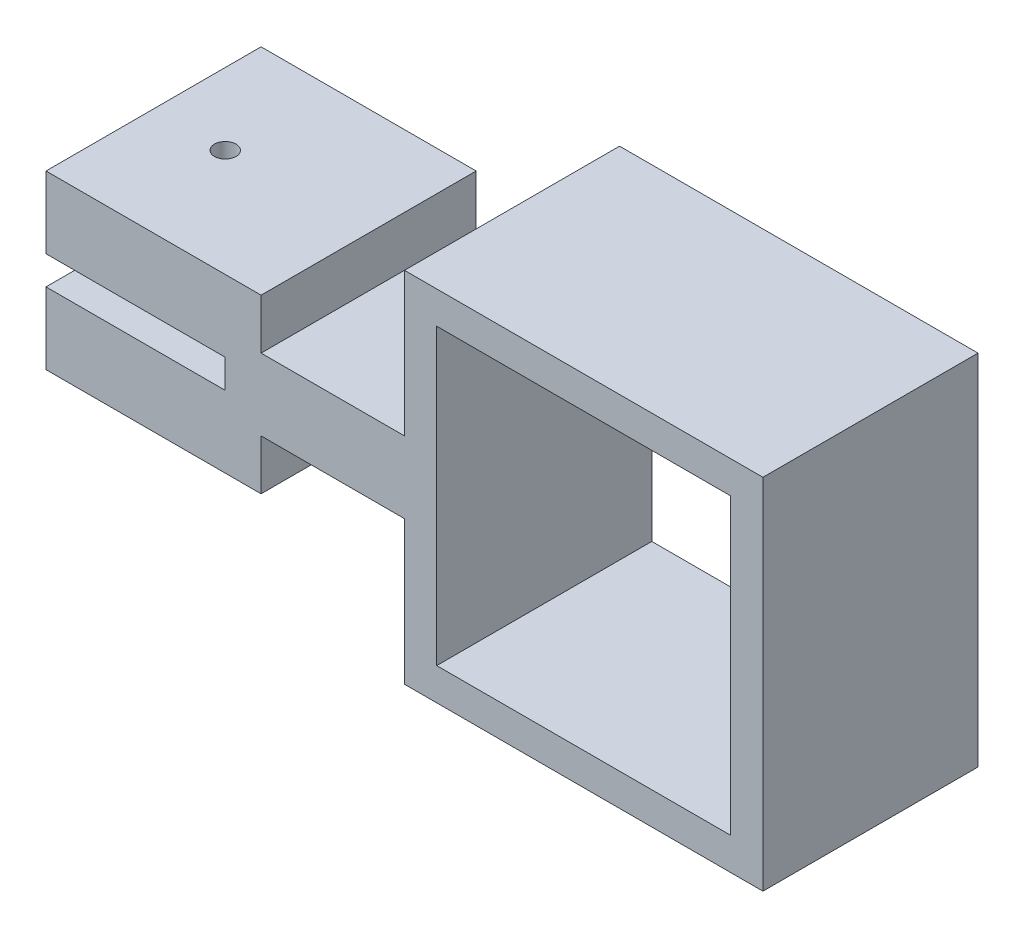
SolidWorks part; units mm, degrees
ref_plane "前视基准面" through (0, 0, 0) normal (0, 0, 1) x (1, 0, 0)
ref_plane "上视基准面" through (0, 0, 0) normal (0, 1, 0) x (1, 0, 0)
ref_plane "右视基准面" through (0, 0, 0) normal (1, 0, 0) x (0, 0, -1)
sketch "草图1" plane through (0, 0, 0) normal (0, 0, 1) x (1, 0, 0)
  line L68 (-21.1315, 0) -> (10.2214, 0) construction
  line L78 (-50, 12) -> (-50, 2)
  line L79 (-50, 12) -> (-20, 12)
  line L80 (-20, 12) -> (-20, 5)
  line L81 (-20, 5) -> (0, 5)
  line L82 (-50, 2) -> (-25, 2)
  line L83 (0, 5) -> (0, 25)
  line L84 (0, 25) -> (50, 25)
  line L85 (0, -25) -> (50, -25)
  line L86 (0, -5) -> (0, -25)
  line L87 (-50, -2) -> (-25, -2)
  line L88 (-20, -5) -> (0, -5)
  line L89 (-20, -12) -> (-20, -5)
  line L90 (-50, -12) -> (-20, -12)
  line L91 (-50, -12) -> (-50, -2)
  line L92 (-25, 2) -> (-25, -2)
  line L93 (50, 25) -> (50, -25)
  dimension "D1" = 30
  dimension "D2" = 10
  dimension "D3" = 4
  dimension "D4" = 25
  dimension "D5" = 7
  dimension "D6" = 20
  dimension "D7" = 20
  dimension "D8" = 50
extrude "凸台-拉伸1" add sketch "草图1" along normal blind 30 contours L78 L82 L92 L87 L91 L90 L89 L88 L86 L85 L93 L84 L83 L81 L80 L79
sketch "草图5" plane through (0, 0, 30) normal (0, 0, 1) x (1, 0, 0)
  line L0 (4.5, 20.5) -> (4.5, -20.5)
  line L1 (4.5, -20.5) -> (45.5, -20.5)
  line L3 (45.5, 20.5) -> (4.5, 20.5)
  line L4 (4.5, 20.5) -> (4.5, 25) construction
  line L5 (0, 25) -> (50, 25) construction
  line L6 (4.5, -20.5) -> (0, -20.5) construction
  line L7 (0, -5) -> (0, -25) construction
  line L17 (45.5, 20.5) -> (45.5, -20.5)
  dimension "D1" = 41
  dimension "D2" = 41
  dimension "D3" = 4.5
  dimension "D4" = 4.5
extrude "切除-拉伸1" cut sketch "草图5" against normal blind 30
sketch "草图7" plane through (0, 12, 0) normal (0, 1, 0) x (1, 0, 0)
  line L0 (-40, -15) -> (-50, -15) construction
  line L2 (-50, -30) -> (-50, 0) construction
  line L3 (-40, -15) -> (-40, 0) construction
  line L4 (-50, 0) -> (-20, 0) construction
  circle A0 centre (-40, -15) radius 1.5
  dimension "D1" = 3
  dimension "D2" = 10
  dimension "D3" = 15
extrude "切除-拉伸5" cut sketch "草图7" against normal up to surface (24 mm away) up to face at (-35, -12, 15)
